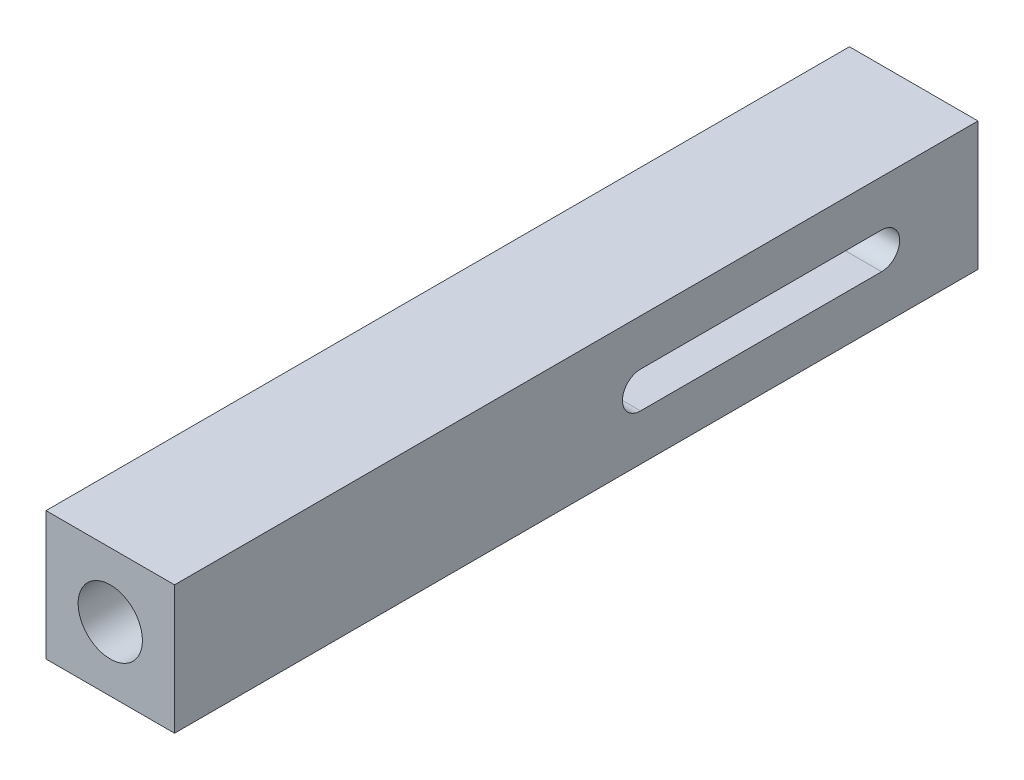
SolidWorks part; units mm, degrees
ref_plane "Front Plane" through (0, 0, 0) normal (0, 0, 1) x (1, 0, 0)
ref_plane "Top Plane" through (0, 0, 0) normal (0, 1, 0) x (1, 0, 0)
ref_plane "Right Plane" through (0, 0, 0) normal (1, 0, 0) x (0, 0, -1)
sketch "Sketch1" plane through (0, 0, 0) normal (0, 0, 1) x (1, 0, 0)
  line L1 (8, -8) -> (-8, -8)
  line L2 (8, -8) -> (8, 8)
  line L3 (8, 8) -> (-8, 8)
  line L4 (-8, -8) -> (-8, 8)
  line L5 (8, -8) -> (-8, 8) construction
  line L6 (8, 8) -> (-8, -8) construction
  circle A0 centre (0, 0) radius 4
  point P0 (0, 0)
  dimension "D3" = 8
  dimension "D1" = 16
  dimension "D2" = 16
extrude "Boss-Extrude1" add sketch "Sketch1" along normal blind 100
sketch "Sketch2" plane through (8, 0, 0) normal (1, 0, 0) x (0, 0, -1)
  line L0 (0, 0) -> (-84.7501, 0) construction
  line L1 (0, -8) -> (0, 8) construction
  line L2 (-42, 2.25) -> (-12, 2.25)
  line L3 (-42, -2.25) -> (-12, -2.25)
  arc A0 (-12, -2.25) -> (-12, 2.25) centre (-12, 0) ccw
  arc A1 (-42, 2.25) -> (-42, -2.25) centre (-42, 0) ccw
  dimension "D1" = 4.5
  dimension "D2" = 4.5
  dimension "D3" = 12
  dimension "D4" = 30
extrude "Cut-Extrude1" cut sketch "Sketch2" against normal through all
ref_axis "Axis1" through (0, 0, -4.2375) along (0, 0, 1)
